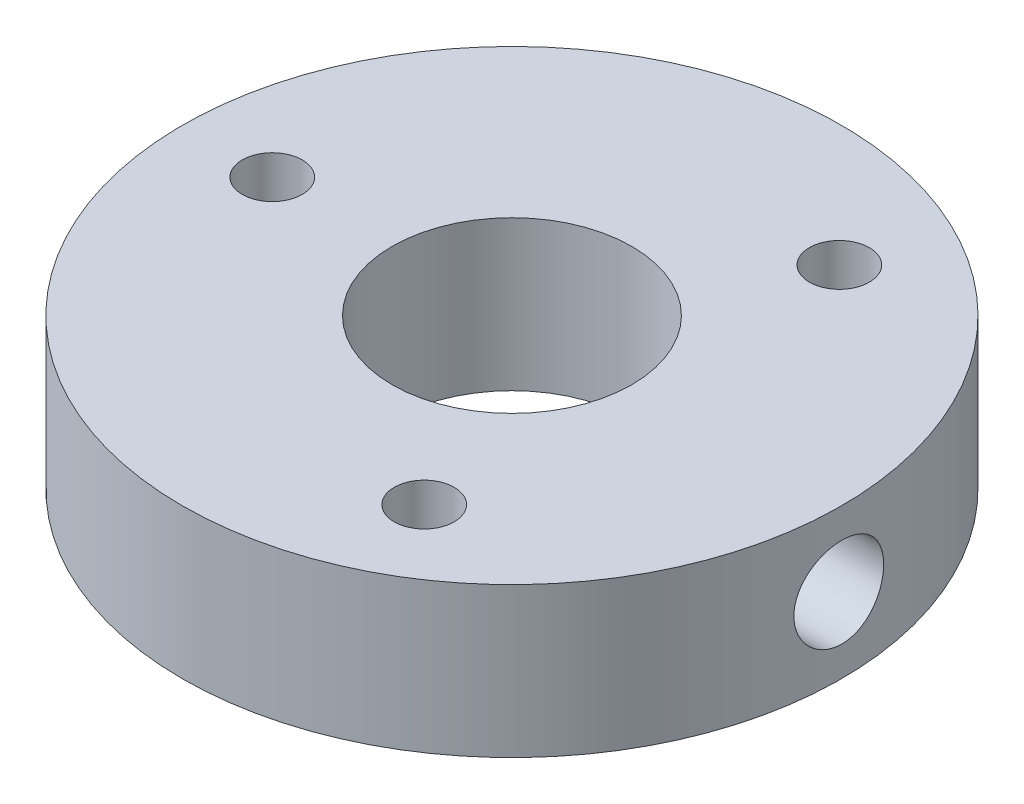
SolidWorks part; units mm, degrees
ref_plane "Front Plane" through (0, 0, 0) normal (0, 0, 1) x (1, 0, 0)
ref_plane "Top Plane" through (0, 0, 0) normal (0, 1, 0) x (1, 0, 0)
ref_plane "Right Plane" through (0, 0, 0) normal (1, 0, 0) x (0, 0, -1)
sketch "Sketch1" plane through (0, 0, 0) normal (0, 1, 0) x (1, 0, 0)
  line L0 (0, 0) -> (-8, 0) construction
  line L1 (0, 0) -> (4, 6.9282) construction
  line L2 (0, 0) -> (4, -6.9282) construction
  circle A0 centre (0, 0) radius 4
  circle A1 centre (-8, 0) radius 1
  circle A2 centre (4, 6.9282) radius 1
  circle A3 centre (4, -6.9282) radius 1
  circle A4 centre (0, 0) radius 11
  point P7 (0, 0)
  point P10 (0, 0)
  point P12 (0, 0)
extrude "Boss-Extrude1" add sketch "Sketch1" along normal blind 5
sketch3d "3DSketch1"
  point P0 (10.9987, 4.2005, -0.1708)
ref_plane "Plane1" through (10.9987, 0, 0) normal (1, 0, 0) x (0, 0, -1)
sketch "Sketch2" plane through (10.9987, 0, 0) normal (1, 0, 0) x (0, 0, -1)
  line L0 (0, 0) -> (0.0116, 2.5) construction
  circle A0 centre (0.0116, 2.5) radius 1.5
extrude "Cut-Extrude1" cut sketch "Sketch2" against normal blind 10 and the other way blind 10
